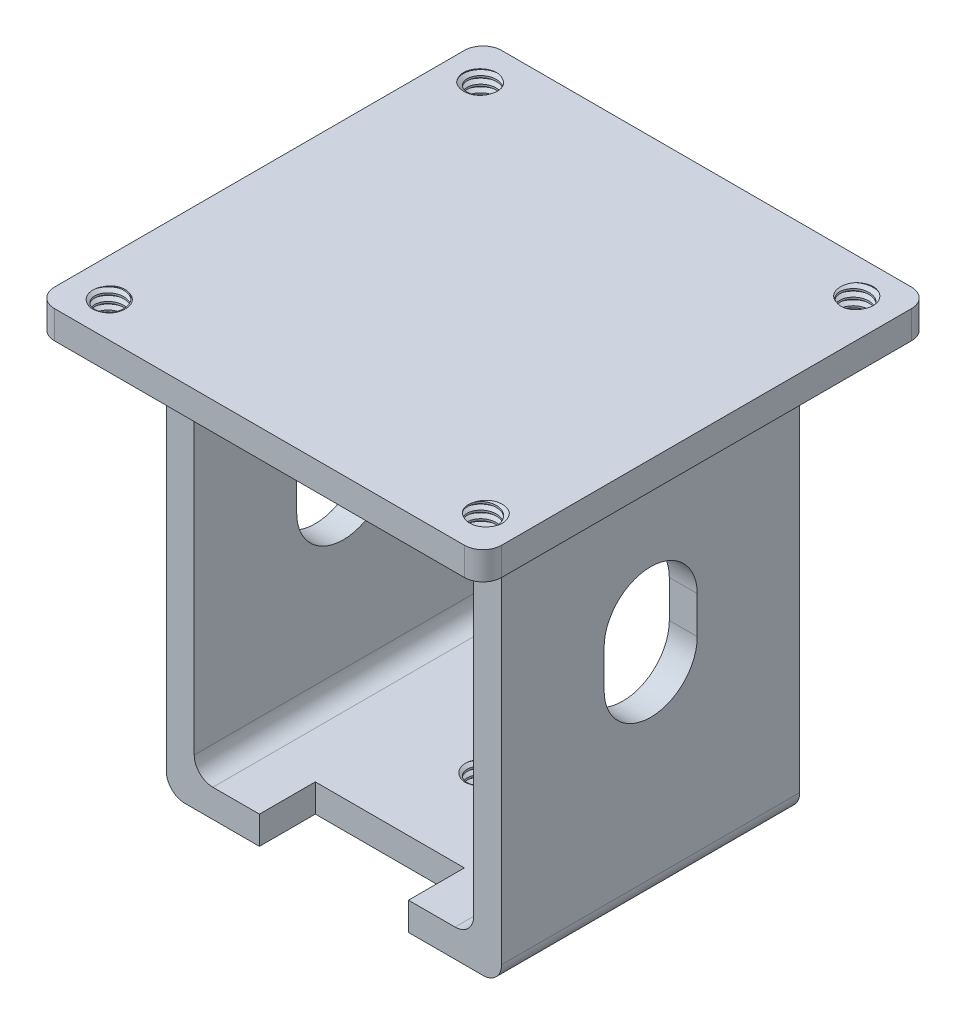
SolidWorks part; units mm, degrees
ref_plane "Front Plane" through (0, 0, 0) normal (0, 0, 1) x (1, 0, 0)
ref_plane "Top Plane" through (0, 0, 0) normal (0, 1, 0) x (1, 0, 0)
ref_plane "Right Plane" through (0, 0, 0) normal (1, 0, 0) x (0, 0, -1)
sketch "Sketch1" plane through (0, 0, 0) normal (0, 0, 1) x (1, 0, 0)
  line L0 (0, 0) -> (0, 69.85)
  line L1 (0, 69.85) -> (-9.525, 69.85)
  line L2 (-9.525, 69.85) -> (-9.525, 74.6125)
  line L3 (-9.525, 74.6125) -> (66.675, 74.6125)
  line L4 (66.675, 74.6125) -> (66.675, 69.85)
  line L5 (66.675, 69.85) -> (57.15, 69.85)
  line L6 (57.15, 69.85) -> (57.15, 0)
  line L7 (57.15, 0) -> (0, 0)
  line L10 (4.7625, 4.7625) -> (52.3875, 4.7625)
  line L11 (4.7625, 4.7625) -> (4.7625, 69.85)
  line L12 (4.7625, 69.85) -> (52.3875, 69.85)
  line L13 (52.3875, 4.7625) -> (52.3875, 69.85)
  line L14 (4.7625, 4.7625) -> (52.3875, 69.85) construction
  line L15 (4.7625, 69.85) -> (52.3875, 4.7625) construction
  point P7 (28.575, 74.6125)
  point P10 (28.575, 0)
  point P13 (28.575, 37.3062)
  dimension "D1" = 69.85
  dimension "D3" = 57.15
  dimension "D4" = 76.2
  dimension "D5" = 4.7625
  dimension "D6" = 4.7625
  dimension "D7" = 4.7625
  dimension "D8" = 4.7625
extrude "Boss-Extrude1" add sketch "Sketch1" along normal blind 50.8
sketch "Sketch2" plane through (0, 0, 0) normal (0, -1, 0) x (1, 0, 0)
  line L0 (0, 25.4) -> (57.15, 25.4) construction
  line L1 (0, 50.8) -> (0, 0) construction
  line L2 (57.15, 50.8) -> (57.15, 0) construction
  line L3 (28.575, 0) -> (28.575, 50.8) construction
  line L4 (0, 0) -> (57.15, 0) construction
  line L5 (0, 50.8) -> (57.15, 50.8) construction
  circle A0 centre (28.575, 25.4) radius 3.175
  dimension "D1" = 6.35
extrude "Cut-Extrude1" cut sketch "Sketch2" against normal up to next
thread "Thread1" pitch 1.27 start angle 0, offset 0, length 0, pitch 1.27, diameter 6.35
ref_plane "Plane1" through (31.75, 0, 25.4) normal (0, 0, 1) x (1, 0, 0)
sketch "Thread Profile1" plane through (31.75, 0, 25.4) normal (0, 0, 1) x (1, 0, 0)
  line L0 (0, 0) -> (0, 1.27) construction
  line L11 (0, 0) -> (0, 1.1112)
  line L12 (0, 1.1112) -> (-0.6874, 0.7144)
  line L13 (-0.6874, 0.7144) -> (-0.6874, 0.3969)
  line L15 (-0.6874, 0.3969) -> (0, 0)
  line L17 (-0.6874, 0.5556) -> (0, 0.5556) construction
  point P2 (0, 0)
  dimension "Pitch" = 1.27
  dimension "Profile_Angle" = 60
  dimension "Profile_Land" = 0.3175
  dimension "Profile_Height" = 0.6874
sketch "Sketch6" plane through (0, 0, 0) normal (0, 0, -1) x (-1, 0, 0)
  line L1 (-52.3875, 69.85) -> (-4.7625, 69.85)
  line L2 (-52.3875, 69.85) -> (-52.3875, 4.7625)
  line L3 (-52.3875, 4.7625) -> (-4.7625, 4.7625)
  line L4 (-4.7625, 69.85) -> (-4.7625, 4.7625)
extrude "Cut-Extrude2" cut sketch "Sketch6" along direction (0, 0, -1) on the side against the normal up to next (50.8 mm away)
sketch "Sketch7" plane through (4.7625, 0, 0) normal (1, 0, 0) x (0, 0, -1)
  line L0 (-50.8, 38.1) -> (0, 38.1) construction
  line L1 (-50.8, 69.85) -> (-50.8, 0) construction
  line L2 (0, 69.85) -> (0, 0) construction
  line L3 (-25.4, 41.275) -> (-25.4, 34.925) construction
  line L4 (-17.4625, 41.275) -> (-17.4625, 34.925)
  line L5 (-33.3375, 41.275) -> (-33.3375, 34.925)
  line L6 (-50.8, 69.85) -> (0, 69.85) construction
  arc A1 (-17.4625, 41.275) -> (-33.3375, 41.275) centre (-25.4, 41.275) ccw
  arc A2 (-33.3375, 34.925) -> (-17.4625, 34.925) centre (-25.4, 34.925) ccw
  point P8 (-25.4, 38.1)
  point P13 (-25.4, 38.1)
  dimension "D1" = 7.9375
  dimension "D2" = 6.35
  dimension "D3" = 31.75
extrude "Cut-Extrude3" cut sketch "Sketch7" against normal through all both and the other way through all
sketch "Sketch9" plane through (0, 0, 0) normal (0, -1, 0) x (1, 0, 0)
  line L0 (28.575, 50.8) -> (28.575, 0) construction
  line L1 (0, 50.8) -> (57.15, 50.8) construction
  line L2 (0, 0) -> (57.15, 0) construction
  line L3 (15.875, 50.8) -> (15.875, 41.275)
  line L4 (15.875, 41.275) -> (41.275, 41.275)
  line L5 (57.15, 25.4) -> (0, 25.4) construction
  line L6 (0, 50.8) -> (0, 0) construction
  line L7 (15.875, 0) -> (15.875, 9.525)
  line L8 (15.875, 9.525) -> (41.275, 9.525)
  line L9 (41.275, 0) -> (41.275, 9.525)
  line L10 (41.275, 50.8) -> (41.275, 41.275)
  line L11 (15.875, 50.8) -> (41.275, 50.8)
  line L12 (15.875, 0) -> (41.275, 0)
  point P18 (28.575, 9.525)
  point P19 (28.575, 25.4)
  point P21 (28.575, 41.275)
  dimension "D1" = 12.7
  dimension "D2" = 9.525
extrude "Cut-Extrude4" cut sketch "Sketch9" against normal up to next and the other way through all contours L11 L10 L4 L3 | L12 L9 L8 L7
sketch "Sketch12" plane through (0, 0, 0) normal (0, 0, -1) x (-1, 0, 0)
  line L1 (-66.675, 69.85) -> (9.525, 69.85)
  line L2 (-66.675, 69.85) -> (-66.675, 74.6125)
  line L3 (-66.675, 74.6125) -> (9.525, 74.6125)
  line L4 (9.525, 69.85) -> (9.525, 74.6125)
extrude "Boss-Extrude3" add sketch "Sketch12" along normal blind 12.7 contours L2 L1 L4 L3
sketch "Sketch13" plane through (0, 0, 50.8) normal (0, 0, 1) x (1, 0, 0)
  line L1 (66.675, 74.6125) -> (-9.525, 74.6125)
  line L2 (66.675, 74.6125) -> (66.675, 69.85)
  line L3 (66.675, 69.85) -> (-9.525, 69.85)
  line L4 (-9.525, 74.6125) -> (-9.525, 69.85)
extrude "Boss-Extrude4" add sketch "Sketch13" along normal blind 12.7
sketch "Sketch14" plane through (0, 69.85, 0) normal (0, -1, 0) x (-1, 0, 0)
  line L0 (9.525, -63.5) -> (9.525, 12.7) construction
  line L1 (9.525, -63.5) -> (-66.675, -63.5) construction
  line L2 (-28.575, -63.5) -> (-28.575, 12.7) construction
  line L3 (-66.675, 12.7) -> (9.525, 12.7) construction
  line L4 (-66.675, -25.4) -> (9.525, -25.4) construction
  line L5 (-66.675, -63.5) -> (-66.675, 12.7) construction
  circle A0 centre (3.175, -57.15) radius 3.175
  circle A1 centre (3.175, 6.35) radius 3.175
  circle A2 centre (-60.325, -57.15) radius 3.175
  circle A3 centre (-60.325, 6.35) radius 3.175
  dimension "D3" = 6.35
  dimension "D1" = 6.35
  dimension "D2" = 6.35
extrude "Cut-Extrude5" cut sketch "Sketch14" against normal up to next
thread "Thread2" pitch 1.27 profile "Thread Profile2" start angle 0, offset 0, length 0, pitch 1.27, diameter 6.35
ref_plane "Plane2" through (0, 69.85, 57.15) normal (0, 0, 1) x (1, 0, 0)
sketch "Thread Profile2" plane through (0, 69.85, 57.15) normal (0, 0, 1) x (1, 0, 0)
  line L0 (0, 0) -> (0, 1.27) construction
  line L11 (0, 0) -> (0, 1.1112)
  line L12 (0, 1.1112) -> (-0.6874, 0.7144)
  line L13 (-0.6874, 0.7144) -> (-0.6874, 0.3969)
  line L15 (-0.6874, 0.3969) -> (0, 0)
  line L17 (-0.6874, 0.5556) -> (0, 0.5556) construction
  point P2 (0, 0)
  dimension "Pitch" = 1.27
  dimension "Profile_Angle" = 60
  dimension "Profile_Land" = 0.3175
  dimension "Profile_Height" = 0.6874
pattern_circular "CirPattern1" count 4 over 360 of "Thread2"
sketch "Sketch17" plane through (66.675, 0, 0) normal (1, 0, 0) x (0, 0, -1)
  line L1 (-63.5, 74.6125) -> (12.7, 74.6125)
  line L2 (-63.5, 74.6125) -> (-63.5, 76.0612)
  line L3 (-63.5, 76.0612) -> (12.7, 76.0612)
  line L4 (12.7, 74.6125) -> (12.7, 76.0612)
  dimension "D1" = 1.4487
extrude "Cut-Extrude6" cut sketch "Sketch17" along direction (1, 0, 0) on the side against the normal up to surface (76.2 mm away) contours L2 L1 L4 L3
fillet "Fillet1" radius 3.175 4 edges at (-9.525, 72.2313, -12.7) (66.675, 72.2313, -12.7) (66.675, 72.2313, 63.5) (-9.525, 72.2313, 63.5)
fillet "Fillet2" radius 3.175 4 edges at (4.7625, 4.7625, 25.4) (52.3875, 4.7625, 25.4) (57.15, 0, 25.4) (0, 0, 25.4)
